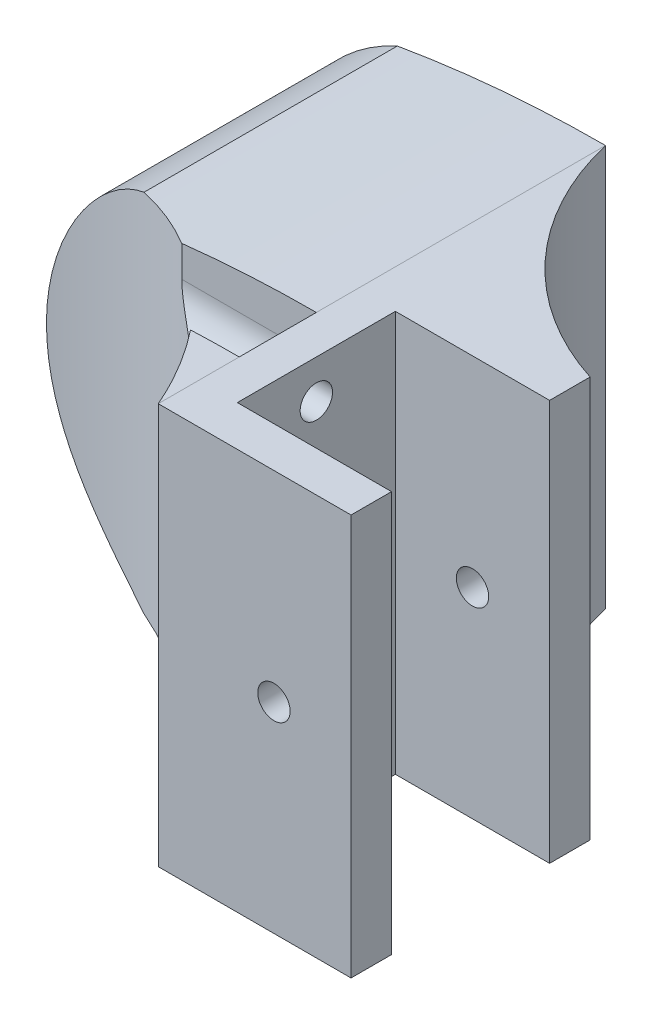
SolidWorks part; units mm, degrees
material "PBT Общее назначение"
ref_plane "Спереди" through (0, 0, 0) normal (0, 0, 1) x (1, 0, 0)
ref_plane "Сверху" through (0, 0, 0) normal (0, 1, 0) x (1, 0, 0)
ref_plane "Справа" through (0, 0, 0) normal (1, 0, 0) x (0, 0, -1)
sketch "Эскиз1" plane through (0, 0, 0) normal (0, 0, 1) x (1, 0, 0)
  line L0 (0, 0) -> (61.556, 0) construction
  line L1 (0, 26) -> (0, -26)
  line L2 (0, 26) -> (52, 26)
  line L3 (0, -26) -> (52, -26)
  line L4 (52, 26) -> (52, -26)
  line L5 (0, 0) -> (52, 0) construction
  dimension "D1" = 52
  dimension "D2" = 52
extrude "Бобышка-Вытянуть1" add sketch "Эскиз1" along normal blind 31
sketch "Эскиз2" plane through (0, 0, 0) normal (-1, 0, 0) x (0, 0, 1)
  line L0 (15.5, 26) -> (15.5, -26) construction
  line L1 (31, 26) -> (0, 26) construction
  line L2 (31, -26) -> (0, -26) construction
  line L3 (5.25, 26) -> (25.75, 26)
  line L4 (5.25, 26) -> (5.25, -26)
  line L5 (25.75, 26) -> (25.75, -26)
  line L6 (5.25, -26) -> (25.75, -26)
  line L7 (15.5, 26) -> (15.5, -26) construction
  dimension "D1" = 20.5
extrude "Вырез-Вытянуть1" cut sketch "Эскиз2" against normal blind 20
sketch "Эскиз3" plane through (52, 0, 0) normal (1, 0, 0) x (0, 0, -1)
  line L0 (-15.5, 26) -> (-15.5, -26) construction
  line L1 (-31, 26) -> (0, 26) construction
  line L2 (-31, -26) -> (0, -26) construction
  line L3 (-31, 0) -> (0, 0) construction
  line L4 (-31, -26) -> (-31, 26) construction
  line L5 (0, -26) -> (0, 26) construction
ref_plane "СимZ" through (0, 0, 15.5) normal (0, 0, 1) x (0, -1, 0)
ref_plane "СимY" through (0, 0, 0) normal (0, -1, 0) x (0, 0, -1)
sketch "Эскиз4" plane through (0, 26, 0) normal (0, 1, 0) x (1, 0, 0)
  line L0 (41.25, 0) -> (41.25, -31) construction
  line L1 (52, 0) -> (0, 0) construction
  line L2 (52, -31) -> (0, -31) construction
  line L3 (20, -25.75) -> (20, -5.25) construction
  line L4 (20, -25.75) -> (20, -5.25) construction
  dimension "D1" = 21.25
ref_plane "Симм Лента" through (41.25, 0, 0) normal (-1, 0, 0) x (0, 0, 1)
sketch "Эскиз5" plane through (0, 0, 31) normal (0, 0, 1) x (1, 0, 0)
  line L0 (41.25, 26) -> (41.25, -26) construction
  line L1 (0, -26) -> (52, -26) construction
  line L2 (52, 26) -> (0, 26) construction
  circle A0 centre (41.25, 0) radius 26
extrude "Бобышка-Вытянуть2" add sketch "Эскиз5" against normal up to surface (31 mm away) up to face at (26, 0, 0)
sketch "Эскиз6" plane through (0, 0, 31) normal (0, 0, 1) x (1, 0, 0)
  line L2 (52, 23.6736) -> (52, 26) construction
  line L3 (52, 26) -> (0, 26) construction
  line L4 (52, 23.6736) -> (52, 26)
  line L5 (52, 26) -> (25, 26)
  arc A0 (52, 23.6736) -> (25, 26) centre (25, -131.8405) ccw
  dimension "D1" = 25
extrude "Вырез-Вытянуть2" cut sketch "Эскиз6" against normal through all
mirror "Зеркальное отражение1" about plane through (0, 0, 0) normal (0, -1, 0) of "Вырез-Вытянуть2"
sketch "Эскиз7" plane through (0, 26, 0) normal (0, 1, 0) x (1, 0, 0)
  line L0 (20, -25.75) -> (20, -5.25) construction
  line L1 (20, -25.75) -> (0, -25.75) construction
  line L2 (20, -5.25) -> (0, -5.25) construction
  line L3 (20, -25.75) -> (20, -5.25)
  line L4 (20, -25.75) -> (0, -25.75)
  line L5 (20, -5.25) -> (0, -5.25)
  line L6 (0, -5.25) -> (0, -25.75)
extrude "Вырез-Вытянуть3" cut sketch "Эскиз7" against normal through all
sketch "Эскиз8" plane through (0, 26, 0) normal (0, 1, 0) x (1, 0, 0)
  line L0 (35.2, 15.75) -> (47.3, 15.75) construction
  line L1 (35.2, 15.75) -> (47.3, 15.75) construction
  line L2 (47.3, 8.35) -> (35.2, 8.35) construction
  line L3 (47.3, 8.35) -> (35.2, 8.35) construction
  line L4 (25, 0) -> (0, 0) construction
  dimension "D1" = 8.35
  dimension "D2" = 15.75
sketch "Эскиз9" plane through (0, 0, 0) normal (0, 0, -1) x (-1, 0, 0)
  line L0 (-25, 26) -> (-25, -26)
  arc A0 (-25, 26) -> (-52, 23.6736) centre (-25, -131.8405) ccw construction
  arc A1 (-52, 23.6736) -> (-52, -23.6736) centre (-41.25, 0) ccw construction
  arc A2 (-52, -23.6736) -> (-25, -26) centre (-25, 131.8405) ccw construction
  arc A3 (-25, 26) -> (-52, 23.6736) centre (-25, -131.8405) ccw
  arc A4 (-52, 23.6736) -> (-52, -23.6736) centre (-41.25, 0) ccw
  arc A5 (-52, -23.6736) -> (-25, -26) centre (-25, 131.8405) ccw
extrude "Бобышка-Вытянуть3" add sketch "Эскиз9" along normal blind 27
sketch "Эскиз10" plane through (41.25, 0, 0) normal (-1, 0, 0) x (0, 0, 1)
  line L0 (0, -26) -> (0, 26) construction
  line L1 (0, -26) -> (0, 26) construction
  line L2 (-6.75, 9) -> (-15.75, 9) construction
  line L3 (-6.75, 9) -> (-6.75, -9) construction
  line L4 (-15.75, 9) -> (-15.75, -9) construction
  line L5 (-6.75, -9) -> (-15.75, -9) construction
  line L6 (-15.75, 0) -> (-6.75, 0) construction
  line L7 (-27, -26) -> (-27, 26) construction
  line L8 (-27, -26) -> (-27, 26) construction
  line L9 (-27, 0) -> (0, 0) construction
  line L10 (-11.25, 9) -> (-11.25, -9) construction
  line L11 (-20.75, 14) -> (-1.75, 14)
  line L12 (-20.75, 14) -> (-20.75, 0)
  line L13 (-20.75, 0) -> (-1.75, 0)
  line L14 (-1.75, 0) -> (-1.75, 14)
  dimension "D1" = 15.75
  dimension "D2" = 9
  dimension "D3" = 18
  dimension "D4" = 5
  dimension "D5" = 5
  dimension "D6" = 5
revolve "Вырез-Повернуть2" cut sketch "Эскиз10" angle 360 about L13
sketch "Эскиз11" plane through (0, 0, 0) normal (0, -1, 0) x (0, 0, -1)
  line L0 (1.75, 27.25) -> (1.75, 55.25) construction
  line L1 (1.75, 27.25) -> (1.75, 55.25)
  line L2 (20.75, 55.25) -> (20.75, 27.25) construction
  line L3 (20.75, 55.25) -> (20.75, 27.25)
  line L4 (20.75, 55.25) -> (1.75, 55.25)
  line L5 (20.75, 27.25) -> (1.75, 27.25)
extrude "Вырез-Вытянуть4" cut sketch "Эскиз11" along normal through all
sketch "Эскиз12" plane through (0, -26, 0) normal (0, -1, 0) x (1, 0, 0)
  line L0 (0, 0) -> (25, 0) construction
  line L1 (25, -27) -> (25, 0) construction
  line L2 (0, 0) -> (25, 0)
  line L3 (25, -27) -> (25, 0)
  arc A0 (25, -27) -> (0, 0) centre (-11.4767, -35.7006) ccw
  dimension "D1" = 75
extrude "Бобышка-Вытянуть4" add sketch "Эскиз12" against normal up to surface (52 mm away) up to face at (11.25, 26, 15.5)
sketch "Эскиз13" plane through (0, 0, 31) normal (0, 0, 1) x (1, 0, 0)
  line L0 (10, -26) -> (10, 26) construction
  line L4 (20, 26) -> (0, 26)
  line L5 (20, -26) -> (20, 26)
  line L6 (0, -26) -> (20, -26)
  line L7 (0, 26) -> (0, -26)
  line L8 (20, 26) -> (0, 26) construction
  line L9 (20, -26) -> (20, 26) construction
  line L10 (0, -26) -> (20, -26) construction
  line L11 (0, 26) -> (0, -26) construction
  circle A0 centre (10, 0) radius 2.1
  dimension "D2" = 4.2
  dimension "D1" = 0
extrude "Вырез-Вытянуть5" cut sketch "Эскиз13" against normal through all
sketch "Эскиз14" plane through (20, 0, 0) normal (-1, 0, 0) x (0, 0, 1)
  line L0 (15.5, -26) -> (15.5, 26) construction
  line L4 (5.25, 26) -> (5.25, -26)
  line L5 (5.25, -26) -> (25.75, -26)
  line L6 (25.75, -26) -> (25.75, 26)
  line L7 (25.75, 26) -> (5.25, 26)
  line L8 (5.25, 26) -> (5.25, -26) construction
  line L9 (5.25, -26) -> (25.75, -26) construction
  line L10 (25.75, -26) -> (25.75, 26) construction
  line L11 (25.75, 26) -> (5.25, 26) construction
  circle A0 centre (15.5, -21) radius 2.1
  circle A1 centre (15.5, 21) radius 2.1
  dimension "D2" = 5
  dimension "D3" = 4.2
  dimension "D4" = 4.2
  dimension "D5" = 5
  dimension "D1" = 0
extrude "Вырез-Вытянуть6" cut sketch "Эскиз14" against normal through all
ref_plane "Плоскость1" through (25, 0, 0) normal (1, 0, 0) x (0, 0, -1)
sketch "Эскиз15" plane through (25, 0, 0) normal (1, 0, 0) x (0, 0, -1)
  circle A0 centre (-15.5, 21) radius 2.1 construction
  circle A1 centre (-15.5, 21) radius 2.1 construction
  circle A2 centre (-15.5, -21) radius 2.1 construction
  circle A3 centre (-15.5, -21) radius 2.1 construction
  circle A4 centre (-15.5, 21) radius 5
  circle A5 centre (-15.5, -21) radius 5
  dimension "D1" = 10
  dimension "D2" = 10
extrude "Вырез-Вытянуть7" cut sketch "Эскиз15" along normal through all
sketch "Эскиз16" plane through (20, 0, 0) normal (-1, 0, 0) x (0, 0, 1)
  line L0 (17.6, 21) -> (13.4, 21) construction
  circle A0 centre (15.5, 21) radius 2.1 construction
ref_plane "Плоскость2" through (0, 21, 0) normal (0, 1, 0) x (0, 0, -1)
sketch "Эскиз17" plane through (0, 21, 0) normal (0, 1, 0) x (0, 0, -1)
  line L0 (-20.5, -25) -> (-10.5, -25) construction
  line L1 (-20.5, -25) -> (-10.5, -25)
  line L2 (-10.5, -25) -> (-10.5, -67.25)
  line L3 (-20.5, -25) -> (-20.5, -67.25)
  line L5 (27, -67.25) -> (27, -52) construction
  line L6 (27, -67.25) -> (27, -52) construction
  line L7 (-10.5, -67.25) -> (-20.5, -67.25)
  line L8 (27, -67.25) -> (-10.5, -67.25) construction
extrude "Вырез-Вытянуть8" cut sketch "Эскиз17" along normal through all
mirror "Зеркальное отражение2" about plane through (0, 0, 0) normal (0, -1, 0) of "Вырез-Вытянуть8"
ref_plane "Плоскость3" through (0, 0, 0) normal (0, 0, -1) x (-1, 0, 0)
sketch "Эскиз18" plane through (0, 0, 0) normal (0, 0, -1) x (-1, 0, 0)
  circle A0 centre (-10, 0) radius 2.1 construction
  circle A1 centre (-10, 0) radius 2.1 construction
  circle A2 centre (-10, 0) radius 5
  dimension "D1" = 10
extrude "Вырез-Вытянуть9" cut sketch "Эскиз18" along normal through all
sketch "Эскиз19" plane through (0, 0, 31) normal (0, 0, 1) x (1, 0, 0)
  arc A0 (52, -23.6736) -> (52, 23.6736) centre (41.25, 0) ccw construction
  arc A1 (52, -23.6736) -> (52, 23.6736) centre (41.25, 0) ccw construction
  circle A2 centre (41.25, 0) radius 26 construction
  circle A3 centre (41.25, 0) radius 2.5
  dimension "D1" = 5
extrude "Вырез-Вытянуть10" cut sketch "Эскиз19" against normal through all
ref_plane "Зеркало" through (0, 0, 0) normal (-1, 0, 0) x (0, 0, 1)
mirror "Зеркальное отражение3" about plane through (0, 0, 0) normal (-1, 0, 0) of bodies 147
sketch "Sketch1" plane through (0, 26, 0) normal (0, 1, 0) x (1, 0, 0)
  line L0 (-27.25, 1.75) -> (-52, 1.75) construction
  line L1 (-27.25, 1.75) -> (-52, 1.75) construction
  line L2 (-52, 27) -> (-67.25, 27) construction
  line L3 (-67.25, -31) -> (-52, -31) construction
  line L4 (-52, 27) -> (-67.25, 27) construction
  line L5 (-67.25, -31) -> (-25, -31)
  line L6 (-27.25, -3.25) -> (-67.25, -3.25) construction
  line L7 (-67.25, -31) -> (-67.25, -3.25)
  line L8 (-67.25, -3.25) -> (-67.25, 27) construction
  arc A0 (-25, -31) -> (-67.25, -3.25) centre (-67.25, -49.2883) ccw
  point P11 (-67.25, -3.25)
  dimension "D1" = 5
extrude "Cut-Extrude1" cut sketch "Sketch1" against normal through all
sketch "Sketch2" plane through (0, 0, 0) normal (0, -1, 0) x (0, 0, -1)
  line L0 (27, -43.75) -> (27, -38.75) construction
  line L1 (27, -43.75) -> (27, -38.75) construction
  line L2 (27, -41.25) -> (-65.2716, -41.25) construction
  line L3 (-9.6995, -43.75) -> (-9.6995, 25.882) construction
  arc A0 (-9.6995, -43.75) -> (-13.132, -38.75) centre (-49.2883, -67.25) ccw construction
  arc A1 (-9.6995, -43.75) -> (-13.132, -38.75) centre (-49.2883, -67.25) ccw construction
ref_plane "Plane1" through (0, 0, 9.6995) normal (0, 0, 1) x (1, 0, 0)
sketch "Sketch3" plane through (0, 0, 9.6995) normal (0, 0, 1) x (1, 0, 0)
  circle A0 centre (-41.25, 0) radius 2.5 construction
  circle A1 centre (-41.25, 0) radius 2.5 construction
  circle A2 centre (-41.25, 0) radius 7.5
  dimension "D1" = 15
extrude "Cut-Extrude2" cut sketch "Sketch3" against normal blind 2 and the other way through all
delete or keep bodies "Body-Delete/Keep 1" bodies 147
